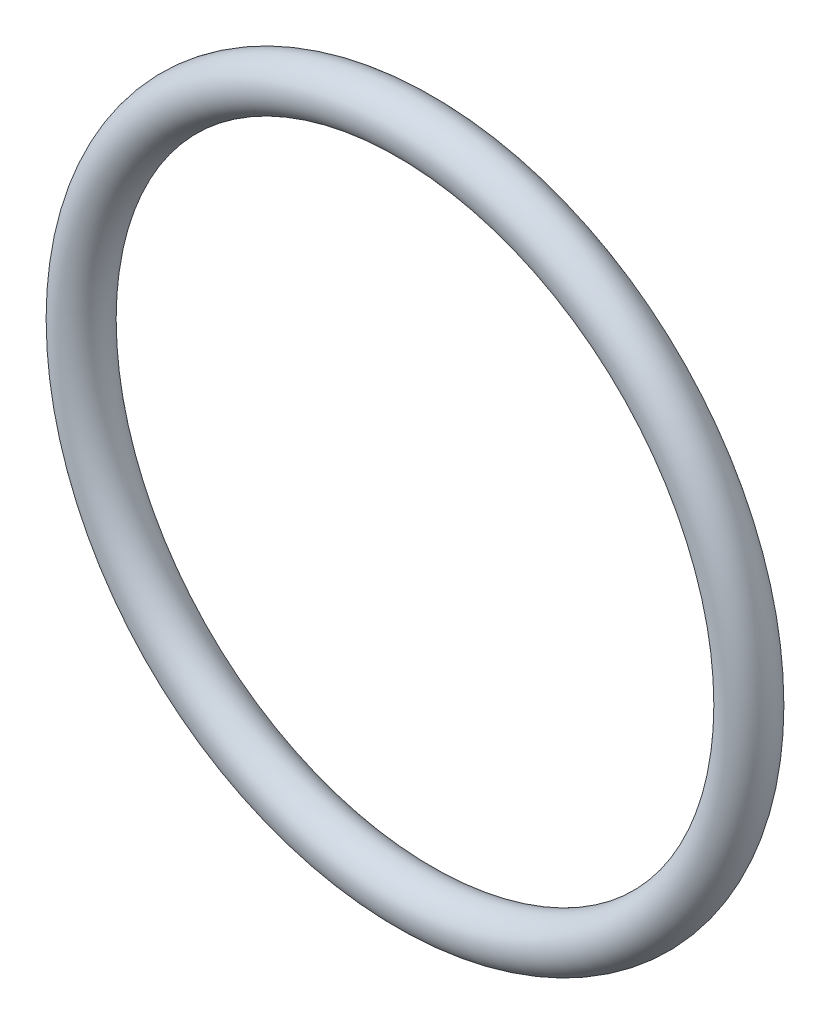
SolidWorks part; units mm, degrees
ref_plane "Front" through (0, 0, 0) normal (0, 0, 1) x (1, 0, 0)
ref_plane "Top" through (0, 0, 0) normal (0, 1, 0) x (1, 0, 0)
ref_plane "Right" through (0, 0, 0) normal (1, 0, 0) x (0, 0, -1)
sketch "Sketch1" plane through (0, 0, 0) normal (1, 0, 0) x (0, -1, 0)
  line L0 (0, -1.7653) -> (0, 1.7653) construction
  line L2 (-28.1076, 0) -> (28.1076, 0) construction
  line L3 (-22.0218, 0) -> (22.0218, 0) construction
  circle A0 centre (23.7871, 0) radius 1.7653
  point P9 (22.0218, 0)
  point P10 (25.5524, 0)
  point P13 (23.7871, 1.7653)
  point P14 (23.7871, -1.7653)
  dimension "Width" = 3.5306
  dimension "ID" = 44.0436
revolve "Revolve1" add sketch "Sketch1" angle 360 about L0
ref_plane "Plane1" through (0, 0, 0) normal (0, 0, 1) x (1, 0, 0)
ref_point "Point1"
ref_axis "Axis1" through (0, 0, 0) along (0, 0, 1)
